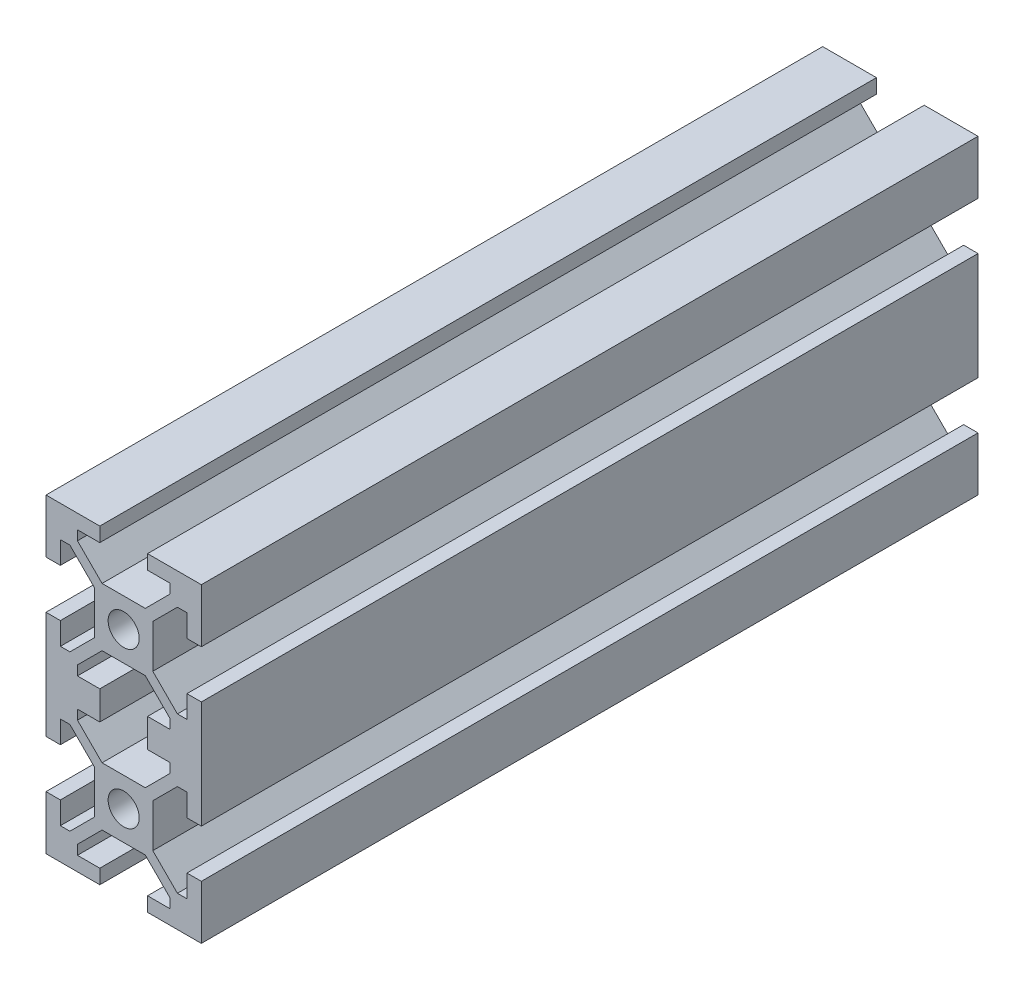
SolidWorks part; units mm, degrees
ref_plane "Front Plane" through (0, 0, 0) normal (0, 0, 1) x (1, 0, 0)
ref_plane "Top Plane" through (0, 0, 0) normal (0, 1, 0) x (1, 0, 0)
ref_plane "Right Plane" through (0, 0, 0) normal (1, 0, 0) x (0, 0, -1)
sketch "Sketch1" plane through (0, 0, 0) normal (0, 0, 1) x (1, 0, 0)
  line L0 (-10, 3.075) -> (-8.15, 3.075)
  line L1 (-10, 10) -> (10, 10) construction
  line L2 (-10, 10) -> (-10, -10) construction
  line L3 (-10, -10) -> (10, -10) construction
  line L4 (10, 10) -> (10, -10) construction
  line L5 (-10, 10) -> (10, -10) construction
  line L6 (-10, -10) -> (10, 10) construction
  line L7 (-8.15, 3.075) -> (-8.15, 5.95)
  line L8 (-8.15, 5.95) -> (-6.9187, 5.95)
  line L9 (-6.9187, 5.95) -> (-3.75, 2.7813)
  line L10 (-3.75, 2.7813) -> (-3.75, 0)
  line L11 (-3.75, 0) -> (-10, 0) construction
  line L12 (-10, 3.075) -> (-10, 10)
  line L13 (-2.7813, 3.75) -> (0, 3.75)
  line L14 (-5.95, 6.9187) -> (-2.7813, 3.75)
  line L15 (-5.95, 8.15) -> (-5.95, 6.9187)
  line L16 (-3.075, 8.15) -> (-5.95, 8.15)
  line L17 (-3.075, 10) -> (-3.075, 8.15)
  line L18 (-3.075, 10) -> (-10, 10)
  line L19 (2.7813, 3.75) -> (0, 3.75)
  line L20 (5.95, 6.9187) -> (2.7813, 3.75)
  line L21 (5.95, 8.15) -> (5.95, 6.9187)
  line L22 (3.075, 8.15) -> (5.95, 8.15)
  line L23 (3.075, 10) -> (3.075, 8.15)
  line L24 (3.075, 10) -> (10, 10)
  line L25 (10, 3.075) -> (10, 10)
  line L26 (10, 3.075) -> (8.15, 3.075)
  line L27 (8.15, 3.075) -> (8.15, 5.95)
  line L28 (8.15, 5.95) -> (6.9187, 5.95)
  line L29 (6.9187, 5.95) -> (3.75, 2.7813)
  line L30 (3.75, 2.7813) -> (3.75, 0)
  line L31 (3.75, -2.7813) -> (3.75, 0)
  line L32 (6.9187, -5.95) -> (3.75, -2.7813)
  line L33 (8.15, -5.95) -> (6.9187, -5.95)
  line L34 (8.15, -3.075) -> (8.15, -5.95)
  line L35 (10, -3.075) -> (8.15, -3.075)
  line L36 (10, -3.075) -> (10, -10)
  line L37 (3.075, -10) -> (10, -10)
  line L38 (3.075, -10) -> (3.075, -8.15)
  line L39 (3.075, -8.15) -> (5.95, -8.15)
  line L40 (5.95, -8.15) -> (5.95, -6.9187)
  line L41 (5.95, -6.9187) -> (2.7813, -3.75)
  line L42 (2.7813, -3.75) -> (0, -3.75)
  line L43 (-2.7813, -3.75) -> (0, -3.75)
  line L44 (-5.95, -6.9187) -> (-2.7813, -3.75)
  line L45 (-5.95, -8.15) -> (-5.95, -6.9187)
  line L46 (-3.075, -8.15) -> (-5.95, -8.15)
  line L47 (-3.075, -10) -> (-3.075, -8.15)
  line L48 (-3.075, -10) -> (-10, -10)
  line L49 (-10, -3.075) -> (-10, -10)
  line L50 (-10, -3.075) -> (-8.15, -3.075)
  line L51 (-8.15, -3.075) -> (-8.15, -5.95)
  line L52 (-8.15, -5.95) -> (-6.9187, -5.95)
  line L53 (-6.9187, -5.95) -> (-3.75, -2.7813)
  line L54 (-3.75, -2.7813) -> (-3.75, 0)
  circle A0 centre (0, 0) radius 2
  point P0 (0, 0)
  point P61 (0, 0)
  dimension "D7" = 4
  dimension "DX" = 20
  dimension "DY" = 20
  dimension "D1" = 6.15
  dimension "D2" = 1.85
  dimension "D3" = 1.37
  dimension "D4" = 4.05
  dimension "D5" = 3.75
  dimension "D6" = 4
extrude "Boss-Extrude1" add sketch "Sketch1" along normal blind 100
pattern_linear "LPattern1" count 2 spacing 20 along (0, 1, 0) of "Boss-Extrude1"
equation "\"DY@Sketch1\"=\"DX@Sketch1\""
equation "\"D5@Sketch1\"=3.75*\"DX@Sketch1\"/20"
equation "\"D4@Sketch1\"=4.05*\"DX@Sketch1\"/20"
equation "\"D3@Sketch1\"=1.37*\"DX@Sketch1\"/20"
equation "\"D1@Sketch1\"=6.15*\"DX@Sketch1\"/20"
equation "\"D3@LPattern1\"=\"DX@Sketch1\""
equation "\"D4@LPattern1\"=\"DX@Sketch1\""
equation "\"D7@Sketch1\"=4*\"DX@Sketch1\"/20"
